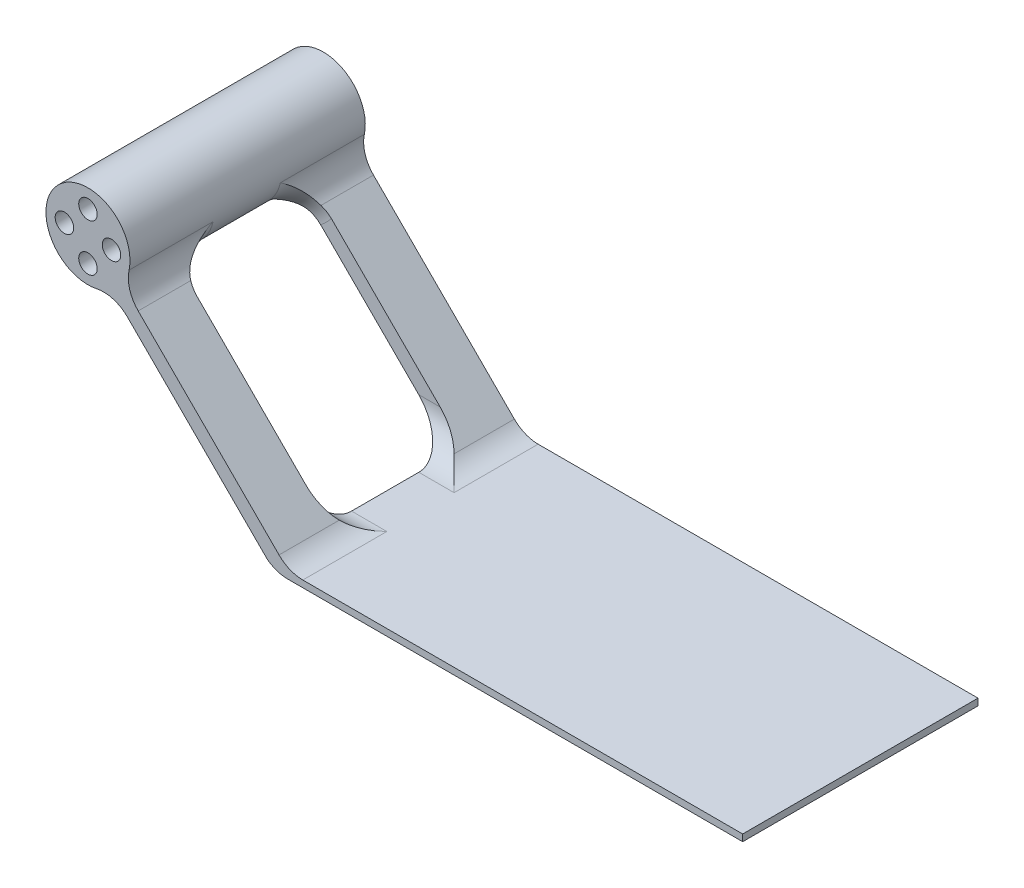
SolidWorks part; units mm, degrees
material "ABS"
ref_plane "Front" through (0, 0, 0) normal (0, 0, 1) x (1, 0, 0)
ref_plane "Top" through (0, 0, 0) normal (0, 1, 0) x (1, 0, 0)
ref_plane "Right" through (0, 0, 0) normal (1, 0, 0) x (0, 0, -1)
sketch "Sketch30" plane through (0, 0, 0) normal (0, 1, 0) x (1, 0, 0)
  line L3 (-70.6823, 10.08) -> (-70.6823, 34)
  line L4 (-70.6823, 34) -> (70.6823, 34)
  line L5 (70.6823, 34) -> (70.6823, -36)
  line L6 (70.6823, -36) -> (-70.6823, -36)
  line L7 (-70.6823, -36) -> (-70.6823, -8.5206)
  line L8 (-70.6823, -8.5206) -> (-70.6823, 10.08)
  dimension "D1" = 70
extrude "Boss-Extrude13" add sketch "Sketch30" along normal blind 2
fillet "Fillet1" radius 10 1 edges at (-70.6823, 0, 1)
sketch "Sketch31" plane through (0, 0, 36) normal (0, 0, 1) x (1, 0, 0)
  line L0 (-70.6823, 2) -> (-120.6823, 52)
  line L1 (-120.6823, 52) -> (-117.5003, 55.182)
  line L2 (-117.5003, 55.182) -> (-64.3183, 2)
  line L3 (-70.6823, 2) -> (70.6823, 2) construction
  line L7 (70.6823, 2) -> (-70.6823, 2)
  line L8 (-64.6823, 0) -> (70.6823, 0)
  line L9 (70.6823, 0) -> (70.6823, 2)
  line L10 (70.6823, 2) -> (-64.3183, 2)
  line L11 (-64.6823, 0) -> (70.6823, 0)
  line L12 (70.6823, 0) -> (70.6823, 2)
  arc A1 (-70.6823, 2) -> (-64.6823, 0) centre (-64.6823, 10) ccw
  arc A3 (-70.6823, 2) -> (-64.6823, 0) centre (-64.6823, 10) ccw
  line M3 (70.6823, 2) -> (-70.6823, 2)
  dimension "D1" = 45
  dimension "D2" = 4.5
  dimension "D3" = 50
  dimension "D4" = 0
extrude "Boss-Extrude17" add sketch "Sketch31" against normal blind 15 contours L2 L1 L0 M3 region at (-93.2713, 27.8037, 36)
fillet "Fillet2" radius 10 2 edges at (-67.5003, 2, 21) (-64.3183, 2, 28.5)
sketch "Sketch36" plane through (0, 0, 0) normal (0, 0, 1) x (1, 0, 0)
  line L0 (-56.5185, -11.4567) -> (-119.0913, 53.591) construction
  line L1 (-120.6823, 52) -> (-117.5003, 55.182) construction
  circle A0 centre (-124.0913, 58.591) radius 12.5
  circle A2 centre (-124.0913, 65.591) radius 2.75
  circle A8 centre (-117.0913, 58.591) radius 2.75
  circle A9 centre (-124.0913, 51.591) radius 2.75
  circle A10 centre (-131.0913, 58.591) radius 2.75
  point P12 (-124.0913, 58.591)
  dimension "D6" = 5.5
  dimension "D9" = 25
  dimension "D1" = 4
  dimension "D2" = 7
extrude "Boss-Extrude19" add sketch "Sketch36" along normal up to surface (36 mm away) contours A0 | A2 | A8 | A9 | A10 up to face at (-45.0075, 14.6151, 36)
mirror "Mirror11" [suppressed]
fillet "Fillet3" [suppressed] radius 10
fillet "Fillet4" [suppressed] radius 20
fillet "Fillet5" [suppressed] radius 10
sketch "Sketch39" plane through (0, 0, 0) normal (0, 0, -1) x (-1, 0, 0)
  circle A0 centre (117.3829, 76.9875) radius 45.0084
extrude "Cut-Extrude3" cut sketch "Sketch39" against normal blind 1
mirror "Mirror14" about plane through (-117.3829, 76.9875, 1) normal (0, 0, -1) of "Boss-Extrude17", "Boss-Extrude19"
fillet "Fillet6" radius 10 2 edges at (-67.5003, 2, -19) (-64.3183, 2, -26.5)
fillet "Fillet7" radius 10 6 edges at (-116.9878, 48.3055, -26.5) (-116.9878, 48.3055, 28.5) (-113.8058, 51.4875, -26.5) (-113.8058, 51.4875, 28.5) (-115.2525, 49.7522, 21) (-115.2525, 49.7522, -19)
